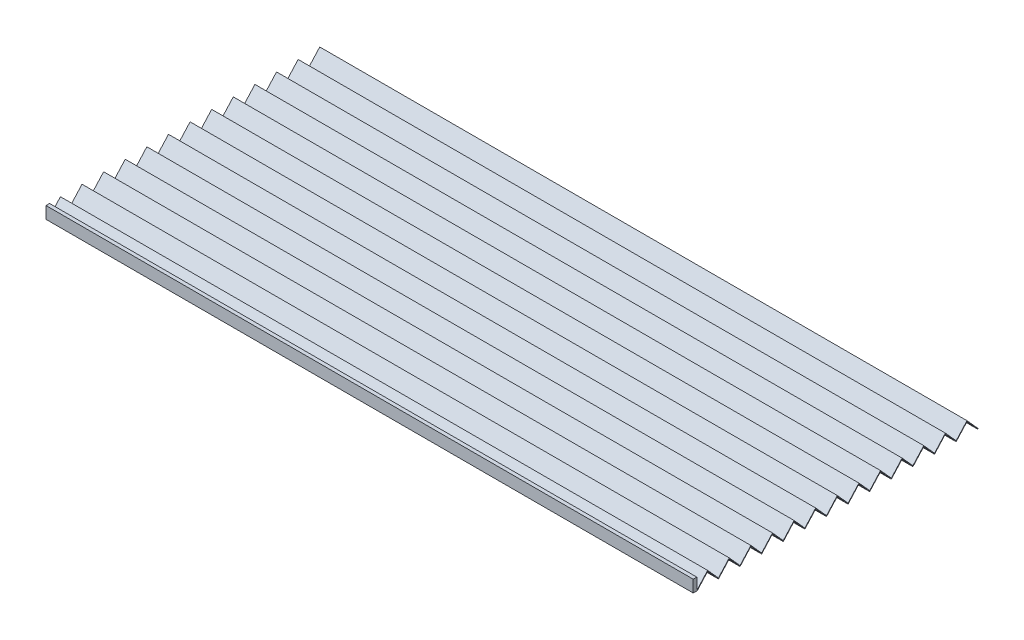
SolidWorks part; units mm, degrees
ref_plane "Front Plane" through (0, 0, 0) normal (0, 0, 1) x (1, 0, 0)
ref_plane "Top Plane" through (0, 0, 0) normal (0, 1, 0) x (1, 0, 0)
ref_plane "Right Plane" through (0, 0, 0) normal (1, 0, 0) x (0, 0, -1)
sketch "Sketch2" plane through (0, 0, 0) normal (0, 0, 1) x (1, 0, 0)
  line L1 (-270, 10) -> (270, 10)
  line L2 (-270, 10) -> (-270, 0)
  line L3 (-270, 0) -> (270, 0)
  line L4 (270, 10) -> (270, 0)
  point P4 (0, 0)
  dimension "D1" = 10
  dimension "D2" = 540
extrude "Boss-Extrude1" add sketch "Sketch2" along normal blind 3
sketch "Sketch3" plane through (270, 0, 0) normal (1, 0, 0) x (0, 0, -1)
  line L0 (0, 10) -> (234.4027, 10) construction
  line L1 (0, 0) -> (234.4027, 0) construction
  line L2 (234.4027, 10) -> (234.4027, 0) construction
  line L3 (0, 0) -> (9.0155, 10)
  line L4 (9.0155, 10) -> (18.031, 0)
  line L5 (18.031, 0) -> (27.0465, 10)
  line L6 (27.0465, 10) -> (36.062, 0)
  line L7 (36.062, 0) -> (45.0775, 10)
  line L8 (45.0775, 10) -> (54.0929, 0)
  line L9 (54.0929, 0) -> (63.1084, 10)
  line L10 (63.1084, 10) -> (72.1239, 0)
  line L11 (72.1239, 0) -> (81.1394, 10)
  line L12 (81.1394, 10) -> (90.1549, 0)
  line L13 (90.1549, 0) -> (99.1704, 10)
  line L14 (99.1704, 10) -> (108.1859, 0)
  line L15 (108.1859, 0) -> (117.2014, 10)
  line L16 (117.2014, 10) -> (126.2169, 0)
  line L17 (126.2169, 0) -> (135.2324, 10)
  line L18 (135.2324, 10) -> (144.2478, 0)
  line L20 (144.2478, 0) -> (153.2633, 10)
  line L21 (153.2633, 10) -> (162.2788, 0)
  line L22 (162.2788, 0) -> (171.2943, 10)
  line L23 (171.2943, 10) -> (180.3098, 0)
  line L24 (180.3098, 0) -> (189.3253, 10)
  line L25 (189.3253, 10) -> (198.3408, 0)
  line L26 (198.3408, 0) -> (207.3563, 10)
  line L27 (207.3563, 10) -> (216.3718, 0)
  line L28 (216.3718, 0) -> (225.3873, 10)
  line L29 (225.3873, 10) -> (234.4027, 0)
  line L30 (234.4027, 10) -> (234.4027, 0) construction
extrude "Extrude-Thin1" add sketch "Sketch3" against normal through all thin thin type mid plane wall 0.5
